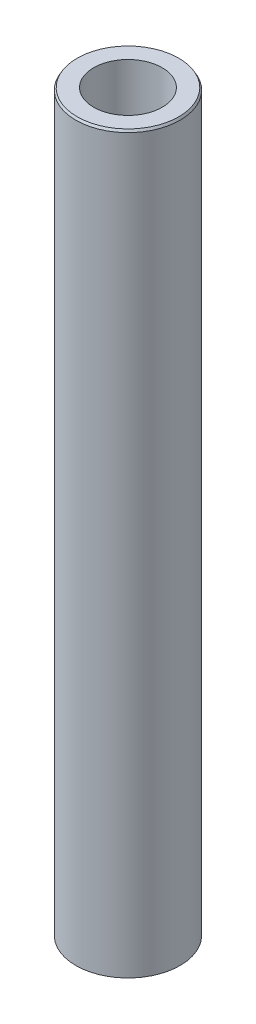
SolidWorks part; units mm, degrees
ref_plane "Front Plane" through (0, 0, 0) normal (0, 0, 1) x (1, 0, 0)
ref_plane "Top Plane" through (0, 0, 0) normal (0, 1, 0) x (1, 0, 0)
ref_plane "Right Plane" through (0, 0, 0) normal (1, 0, 0) x (0, 0, -1)
sketch "Sketch1" plane through (0, 0, 0) normal (0, 1, 0) x (1, 0, 0)
  circle A0 centre (0, 0) radius 42.5
  dimension "SHAFT_OD" = 85
extrude "Boss-Extrude1" add sketch "Sketch1" along normal blind 600
sketch "Sketch2" plane through (0, 0, 0) normal (0, 1, 0) x (1, 0, 0)
  circle A0 centre (0, 0) radius 27.9581
  dimension "BORE_D" = 55.9162
extrude "Cut-Extrude1" cut sketch "Sketch2" along normal through all
chamfer "Chamfer1" distance 1.866 angle 30 2 edges at (0, 600, 42.5) (0, 0, 42.5) first distance on face at (0, 600, 42.5) first distance on face at (0, 0, 27.9581)
